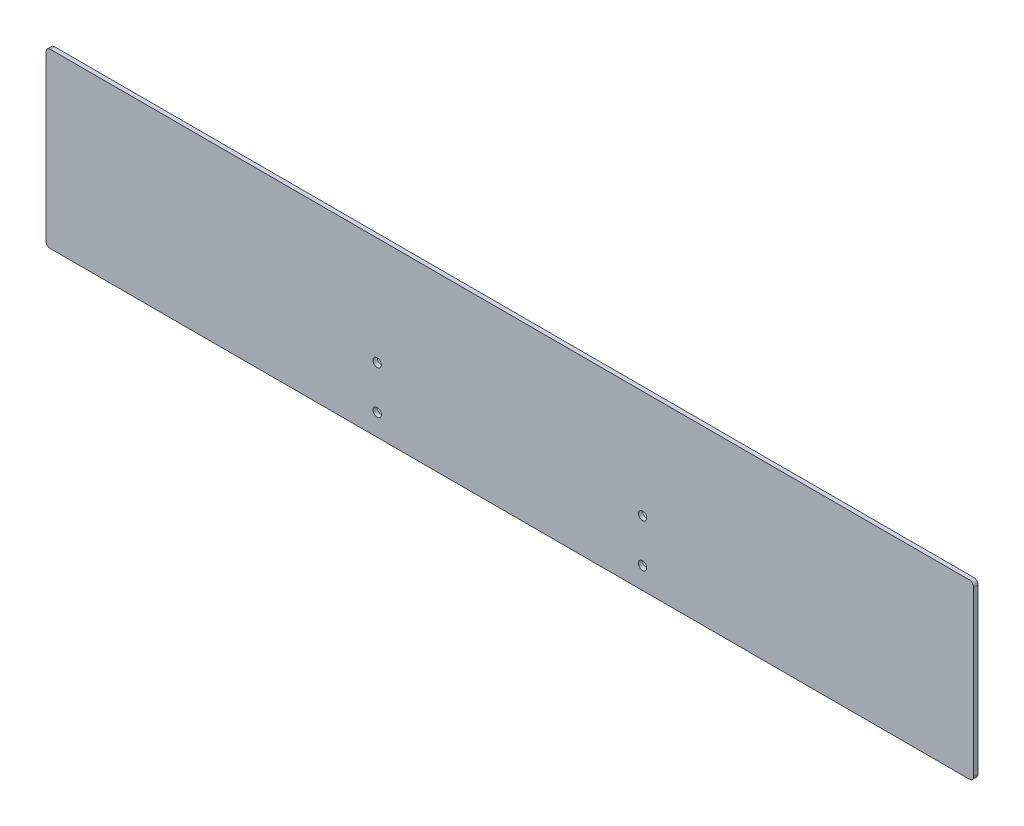
SolidWorks part; units mm, degrees
ref_plane "Front Plane" through (0, 0, 0) normal (0, 0, 1) x (1, 0, 0)
ref_plane "Top Plane" through (0, 0, 0) normal (0, 1, 0) x (1, 0, 0)
ref_plane "Right Plane" through (0, 0, 0) normal (1, 0, 0) x (0, 0, -1)
sketch "Sketch1" plane through (0, 0, 0) normal (0, 0, 1) x (1, 0, 0)
  line L1 (-356.9059, 35.7035) -> (73.0941, 35.7035)
  line L2 (-356.9059, 35.7035) -> (-356.9059, -44.2965)
  line L3 (-356.9059, -44.2965) -> (73.0941, -44.2965)
  line L4 (73.0941, 35.7035) -> (73.0941, -44.2965)
  circle A0 centre (-80.4059, -14.2965) radius 1.95
  circle A1 centre (-80.4059, -34.2965) radius 1.95
  circle A2 centre (-203.4059, -14.2965) radius 1.95
  circle A3 centre (-203.4059, -34.2965) radius 1.95
  point P12 (0, 0)
  point P13 (0, 0)
  point P14 (0, 0)
  point P15 (0, 0)
  dimension "D3" = 123
  dimension "D4" = 20
  dimension "D1" = 430
  dimension "D2" = 80
  dimension "D5" = 10
  dimension "D6" = 153.5
extrude "Boss-Extrude1" add sketch "Sketch1" along normal blind 2
fillet "Fillet1" radius 2 4 edges at (73.0941, 35.7035, 1) (73.0941, -44.2965, 1) (-356.9059, -44.2965, 1) (-356.9059, 35.7035, 1)
